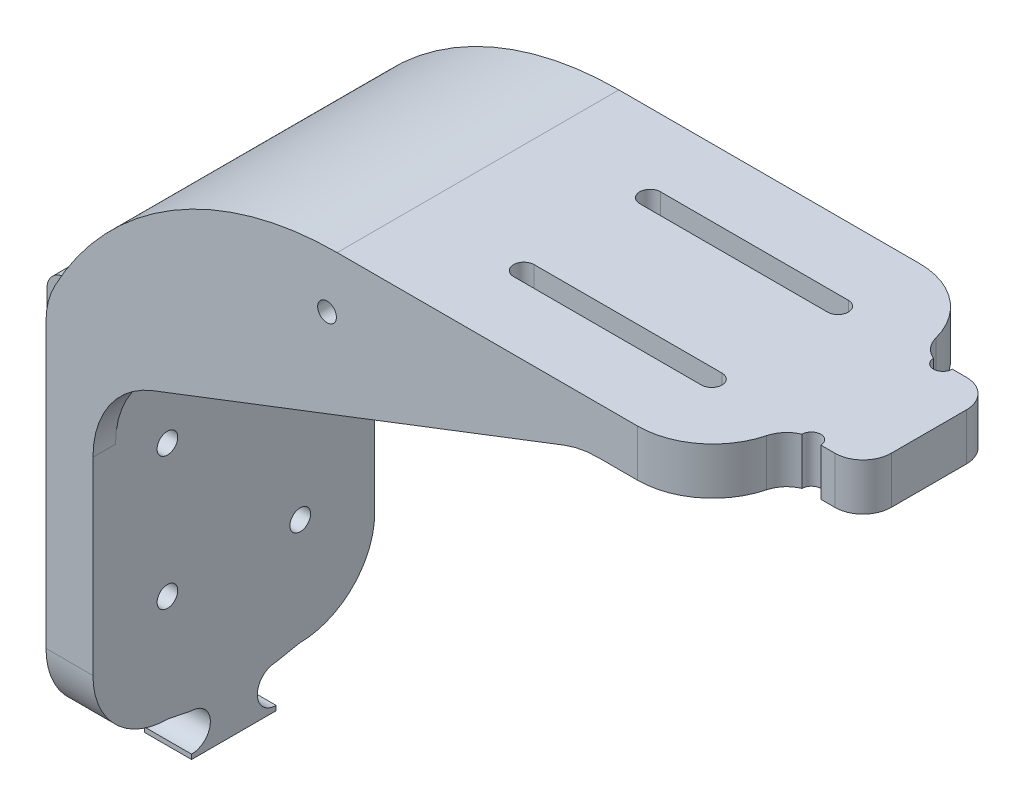
SolidWorks part; units mm, degrees
material "ABS"
ref_plane "Alzado" through (0, 0, 0) normal (0, 0, 1) x (1, 0, 0)
ref_plane "Planta" through (0, 0, 0) normal (0, 1, 0) x (1, 0, 0)
ref_plane "Vista lateral" through (0, 0, 0) normal (1, 0, 0) x (0, 0, -1)
sketch "Croquis1" plane through (0, 0, 0) normal (0, 0, 1) x (1, 0, 0)
  line L0 (0, 0) -> (0, 5)
  line L1 (0, 5) -> (-40, 5)
  line L2 (-40, 5) -> (-71, -15) construction
  line L3 (-71, -15) -> (-71, -55)
  line L4 (-71, -55) -> (-66, -55)
  line L5 (-66, -55) -> (-66, -16.0784)
  line L6 (-66, -16.0784) -> (-41.0784, 0) construction
  line L7 (-41.0784, 0) -> (0, 0)
  line L8 (-53.5392, -8.0392) -> (-39.986, -29.0466) construction
  arc A0 (-40, 5) -> (-71, -15) centre (-39.986, -29.0466) ccw
  arc A1 (-41.0784, 0) -> (-66, -16.0784) centre (-39.986, -29.0466) ccw
  dimension "D1" = 5
  dimension "D2" = 31
  dimension "D4" = 5
  dimension "D5" = 40
  dimension "D6" = 40
  dimension "D7" = 20
  dimension "D8" = 25
extrude "Saliente-Extruir1" add sketch "Croquis1" along normal blind 30
sketch "Croquis2" plane through (0, 5, 0) normal (0, 1, 0) x (1, 0, 0)
  line L0 (0, -30) -> (0, 0) construction
  line L1 (-18.4, -15) -> (-18.4, -12) construction
  line L2 (-18.4, -12) -> (-11.4, -12) construction
  line L4 (-11.4, -18) -> (-25.4, -18) construction
  line L6 (-25.4, -12) -> (-18.4, -12) construction
  line L7 (-18.4, -15) -> (-18.4, -8.28) construction
  line L8 (-18.4, -8.28) -> (-18.4, -7.18) construction
  line L9 (-18.4, -7.18) -> (-8.4, -7.18)
  line L11 (-8.4, -9.38) -> (-28.4, -9.38)
  line L13 (-28.4, -7.18) -> (-18.4, -7.18)
  line L14 (-18.4, -15) -> (-21.0577, -15) construction
  line L19 (-28.4, -9.38) -> (-28.4, -8.28) construction
  line L21 (-28.4, -8.28) -> (-28.4, -7.18) construction
  line L22 (0, -15) -> (-18.4, -15) construction
  line L23 (-8.4, -20.62) -> (-28.4, -20.62)
  line L24 (-18.4, -22.82) -> (-8.4, -22.82)
  line L25 (-28.4, -22.82) -> (-18.4, -22.82)
  circle A0 centre (-18.4, -15) radius 18.4 construction
  arc A1 (-25.4, -18) -> (-25.4, -12) centre (-25.4, -15) cw construction
  arc A2 (-11.4, -18) -> (-11.4, -12) centre (-11.4, -15) ccw construction
  arc A3 (-8.4, -9.38) -> (-8.4, -7.18) centre (-8.4, -8.28) ccw
  arc A4 (-28.4, -9.38) -> (-28.4, -7.18) centre (-28.4, -8.28) cw
  arc A9 (-8.4, -20.62) -> (-8.4, -22.82) centre (-8.4, -21.72) cw
  arc A10 (-28.4, -20.62) -> (-28.4, -22.82) centre (-28.4, -21.72) ccw
  point P28 (-18.4, -9.38)
  dimension "D1" = 36.8
  dimension "D5" = 3
  dimension "D6" = 3
  dimension "D2" = 18.4
  dimension "D3" = 3
  dimension "D4" = 6
  dimension "D7" = 7
  dimension "D8" = 7
  dimension "D9" = 6.72
  dimension "D10" = 2.2
  dimension "D13" = 10
  dimension "D14" = 10
  dimension "D15" = 20
extrude "Cortar-Extruir1" cut sketch "Croquis2" against normal up to vertex (5 mm away) up to point (0, 0, 30)
sketch "Croquis3" plane through (0, 0, 0) normal (0, -1, 0) x (1, 0, 0)
  line L0 (0, 30) -> (0, 0) construction
  line L5 (-28.4, 9.38) -> (-8.4, 9.38) construction
  line L6 (-33.5, 27.6) -> (-3.3, 27.6)
  line L7 (-33.5, 27.6) -> (-33.5, 2.4)
  line L8 (-33.5, 2.4) -> (-3.3, 2.4)
  line L9 (-3.3, 27.6) -> (-3.3, 2.4)
  line L10 (-33.5, 27.6) -> (-3.3, 2.4) construction
  line L11 (-33.5, 2.4) -> (-3.3, 27.6) construction
  line L12 (0, 15) -> (-18.4, 15) construction
  line L13 (-18.4, 15) -> (-18.4, 9.38) construction
  point P0 (-18.4, 15)
  dimension "D1" = 25.2
  dimension "D2" = 30.2
extrude "Cortar-Extruir2" cut sketch "Croquis3" against normal blind 2
sketch "Croquis4" plane through (-71, 0, 0) normal (-1, 0, 0) x (0, 0, 1)
  line L0 (30, -55) -> (0, -55) construction
  line L1 (15, -36.6) -> (21.5109, -36.6) construction
  line L3 (22.0711, -29.5289) -> (15, -36.6) construction
  circle A0 centre (15, -36.6) radius 18.4 construction
  circle A1 centre (22.0711, -29.5289) radius 1.1
  circle A2 centre (22.0711, -43.6711) radius 1.1
  circle A3 centre (7.9289, -43.6711) radius 1.1
  circle A4 centre (7.9289, -29.5289) radius 1.1
  circle A5 centre (15, -36.6) radius 3 construction
  point P15 (15, -36.6)
  dimension "D1" = 36.8
  dimension "D5" = 2.2
  dimension "D7" = 6
  dimension "D2" = 18.4
  dimension "D3" = 45
  dimension "D4" = 10
  dimension "D6" = 4
extrude "Cortar-Extruir3" cut sketch "Croquis4" against normal up to vertex (5 mm away) up to point (-66, -55, 30)
sketch "Croquis5" plane through (-71, 0, 0) normal (-1, 0, 0) x (0, 0, 1)
  line L1 (2.4, -49.2) -> (27.6, -49.2)
  line L2 (2.4, -49.2) -> (2.4, -24)
  line L3 (2.4, -24) -> (27.6, -24)
  line L4 (27.6, -49.2) -> (27.6, -24)
  line L5 (2.4, -49.2) -> (27.6, -24) construction
  line L6 (2.4, -24) -> (27.6, -49.2) construction
  circle A1 centre (22.0711, -29.5289) radius 1.1 construction
  circle A2 centre (7.9289, -29.5289) radius 1.1 construction
  point P0 (15, -36.6)
  dimension "D1" = 25.2
  dimension "D2" = 25.2
  dimension "D3" = 10
  dimension "D4" = 10
extrude "Cortar-Extruir4" cut sketch "Croquis5" against normal blind 2
fillet "Redondeo2" radius 8 5 edges at (-68.5, -55, 0) (-68.5, -55, 30) (0, 2.5, 0) (0, 2.5, 30) (-71, -15, 15)
fillet "Redondeo3" radius 2.7 8 edges at (-70, -49.2, 2.4) (-70, -24, 2.4) (-70, -24, 27.6) (-70, -49.2, 27.6) (-33.5, 1, 2.4) (-33.5, 1, 27.6) (-3.3, 1, 27.6) (-3.3, 1, 2.4)
sketch "Croquis6" plane through (0, 0, 0) normal (0, -1, 0) x (1, 0, 0)
  line L0 (0, 8) -> (0, 22)
  line L1 (0, 22) -> (8, 22)
  line L2 (8, 22) -> (8, 8)
  line L3 (8, 8) -> (0, 8)
  line L7 (0, 22) -> (0, 8) construction
  point P8 (0, 15)
  point P11 (0, 15)
  dimension "D2" = 14
  dimension "D1" = 8
extrude "Saliente-Extruir2" add sketch "Croquis6" against normal up to vertex (5 mm away) up to point (0, 5, 8)
fillet "Redondeo4" radius 3 2 edges at (8, 2.5, 22) (8, 2.5, 8)
sketch "Croquis11" plane through (0, 0, 30) normal (0, 0, 1) x (1, 0, 0)
  line L0 (-41.0784, 0) -> (-14.0784, 0)
  line L1 (-41.0784, 0) -> (-8, 0) construction
  line L2 (-14.0784, 0) -> (-66, -20)
  line L3 (-66, -47) -> (-66, -16.0784) construction
  line L4 (-66, -20) -> (-66, -16.0784)
  line L5 (0, 0) -> (0, -11) construction
  line L6 (0, -11) -> (-42.6353, -11) construction
  arc A2 (-41.0784, 0) -> (-66, -16.0784) centre (-39.986, -29.0466) ccw
  arc A3 (-41.0784, 0) -> (-66, -16.0784) centre (-39.986, -29.0466) ccw
  dimension "D1" = 35
  dimension "D2" = 27
  dimension "D4" = 11
  dimension "D3" = 0
extrude "Saliente-Extruir4" add sketch "Croquis11" against normal up to vertex (2.4 mm away) up to point (-6, 0, 27.6)
extrude "Saliente-Extruir5" add sketch "Croquis11<2>" along normal up to vertex (-27.6 mm away) from surface up to point (-6, 0, 2.4) starting at face at (-49.566, -13.598, 0)
sketch "Croquis11<2>" plane through (0, 0, 30) normal (0, 0, 1) x (1, 0, 0) same geometry as "Croquis11"
fillet "Redondeo5" radius 10 4 edges at (-14.0784, 0, 1.2) (-66, -20, 1.2) (-66, -20, 28.8) (-14.0784, 0, 28.8)
sketch "Croquis12" plane through (-71, 0, 0) normal (-1, 0, 0) x (0, 0, 1)
  line L0 (22, -55) -> (8, -55) construction
  line L1 (10.5, -55) -> (19.5, -55)
  line L3 (10.5, -60) -> (19.5, -60)
  line L8 (22, -55) -> (19.5, -55)
  line L10 (8, -55) -> (10.5, -55)
  line L11 (19.5, -55) -> (19.5, -60) construction
  line L12 (15, -60) -> (15, -55) construction
  line L13 (22, -55) -> (19.5, -55.5)
  line L14 (19.5, -59.5) -> (19.5, -60)
  line L15 (10.5, -59.5) -> (10.5, -60)
  line L16 (10.5, -55) -> (10.5, -60) construction
  line L17 (8, -55) -> (10.5, -55.5)
  arc A2 (19.5, -55.5) -> (19.5, -59.5) centre (19.5, -57.5) ccw
  arc A3 (10.5, -55.5) -> (10.5, -59.5) centre (10.5, -57.5) cw
  point P6 (15, -55)
  point P7 (15, -55)
  point P8 (15, -60)
  dimension "D3" = 2
  dimension "D1" = 9
  dimension "D2" = 5
extrude "Saliente-Extruir6" add sketch "Croquis12" against normal up to vertex (5 mm away) up to point (-66, -55, 8)
sketch "Croquis14" plane through (0, 0, 2.4) normal (0, 0, 1) x (1, 0, 0)
  line L0 (-41.0784, 0) -> (-41.0784, -2.01) construction
  circle A0 centre (-41.0784, -1.005) radius 1
  point P1 (0, 0)
  dimension "D1" = 2
extrude "Cortar-Extruir6" cut sketch "Croquis14" against normal up to vertex (2.4 mm away) and the other way up to vertex (27.6 mm away) up to point (-15.8136, -0.6684, 0) other way up to point (-15.8136, -0.6684, 30)
sketch "Croquis18" plane through (-71, 0, 0) normal (-1, 0, 0) x (0, 0, 1)
  line L0 (30, -16.8489) -> (0, -16.8489) construction
  line L1 (24.9, -24) -> (21.9, -24)
  line L2 (24.9, -24) -> (24.9, -16.8489)
  line L3 (24.9, -16.8489) -> (21.9, -16.8489)
  line L4 (21.9, -24) -> (21.9, -16.8489)
  dimension "D1" = 3
extrude "Saliente-Extruir7" add sketch "Croquis18" along normal blind 5
sketch "Croquis19" plane through (0, 0, 24.9) normal (0, 0, 1) x (1, 0, 0)
  line L0 (-71, -24) -> (-71, -16.8489) construction
  line L1 (-72.625, -22.0494) -> (-72.625, -24)
  line L2 (-76, -24) -> (-71, -24) construction
  line L3 (-72.625, -24) -> (-71, -24)
  line L4 (-71, -24) -> (-71, -20.4244)
  arc A0 (-71, -20.4244) -> (-72.625, -22.0494) centre (-72.625, -20.4244) ccw
  point P11 (-71, -20.4244)
  dimension "D1" = 3.25
extrude "Cortar-Extruir7" cut sketch "Croquis19" against normal up to vertex (3 mm away) up to point (-71, -24, 21.9)
sketch "Croquis20" plane through (0, 2, 0) normal (0, -1, 0) x (1, 0, 0)
  line L8 (-33.5, 24.9) -> (-33.5, 5.1)
  line L9 (-30.8, 2.4) -> (-6, 2.4)
  line L10 (-3.3, 5.1) -> (-3.3, 24.9)
  line L11 (-6, 27.6) -> (-30.8, 27.6)
  line L12 (-33.5, 24.9) -> (-33.5, 5.1)
  line L13 (-30.8, 2.4) -> (-6, 2.4)
  line L14 (-3.3, 5.1) -> (-3.3, 24.9)
  line L15 (-6, 27.6) -> (-30.8, 27.6)
  line L40 (-8.4, 22.82) -> (-28.4, 22.82)
  line L41 (-8.4, 22.82) -> (-28.4, 22.82)
  line L47 (-8.4, 20.62) -> (-28.4, 20.62) construction
  line L49 (-28.4, 7.18) -> (-8.4, 7.18)
  line L50 (-8.4, 9.38) -> (-28.4, 9.38)
  line L51 (-28.4, 7.18) -> (-8.4, 7.18)
  line L52 (-8.4, 9.38) -> (-28.4, 9.38)
  arc A8 (-33.5, 5.1) -> (-30.8, 2.4) centre (-30.8, 5.1) ccw
  arc A9 (-6, 2.4) -> (-3.3, 5.1) centre (-6, 5.1) ccw
  arc A10 (-3.3, 24.9) -> (-6, 27.6) centre (-6, 24.9) ccw
  arc A11 (-30.8, 27.6) -> (-33.5, 24.9) centre (-30.8, 24.9) ccw
  arc A12 (-33.5, 5.1) -> (-30.8, 2.4) centre (-30.8, 5.1) ccw
  arc A13 (-6, 2.4) -> (-3.3, 5.1) centre (-6, 5.1) ccw
  arc A14 (-3.3, 24.9) -> (-6, 27.6) centre (-6, 24.9) ccw
  arc A15 (-30.8, 27.6) -> (-33.5, 24.9) centre (-30.8, 24.9) ccw
  arc A38 (-8.4, 20.62) -> (-8.4, 22.82) centre (-8.4, 21.72) ccw
  arc A39 (-28.4, 22.82) -> (-28.4, 20.62) centre (-28.4, 21.72) ccw
  arc A40 (-8.4, 20.62) -> (-8.4, 22.82) centre (-8.4, 21.72) ccw
  arc A41 (-28.4, 22.82) -> (-28.4, 20.62) centre (-28.4, 21.72) ccw
  arc A46 (-8.4, 7.18) -> (-8.4, 9.38) centre (-8.4, 8.28) ccw
  arc A47 (-28.4, 9.38) -> (-28.4, 7.18) centre (-28.4, 8.28) ccw
  arc A48 (-8.4, 7.18) -> (-8.4, 9.38) centre (-8.4, 8.28) ccw
  arc A49 (-28.4, 9.38) -> (-28.4, 7.18) centre (-28.4, 8.28) ccw
  dimension "D4" = 25.2
  dimension "D5" = 30.2
  dimension "D6" = 20
  dimension "D7" = 11.24
  dimension "D1" = 0
  dimension "D2" = 0
  dimension "D3" = 0
sketch "Croquis22" plane through (0, 0, 0) normal (0, -1, 0) x (1, 0, 0)
  line L0 (5, 22) -> (0, 22) construction
  line L1 (8, 15) -> (0, 15) construction
  line L2 (8, 11) -> (8, 19) construction
  circle A0 centre (2.5, 22) radius 1
  circle A1 centre (2.5, 8) radius 1
  dimension "D1" = 2
extrude "Cortar-Extruir8" cut sketch "Croquis22" against normal up to surface (5 mm away) up to face at (-18.4, 5, 8.28)
fillet "Redondeo8" radius 2 2 edges at (-76, -16.8489, 23.4) (-76, -24, 23.4)
sketch "Croquis23" plane through (0, 0, 2.4) normal (0, 0, 1) x (1, 0, 0)
  line L0 (-41.0784, 0) -> (-30.8, 0)
  arc A0 (-41.0784, 0) -> (-50.8578, -2.0892) centre (-39.986, -29.0466) ccw
  arc A5 (-41.0784, 0) -> (-66, -16.0784) centre (-39.986, -29.0466) ccw construction
  point P5 (-62.1808, -10.2772)
  point P6 (0, 0)
  dimension "D1" = 10
sketch "Croquis24" plane through (-33.5, 0, 0) normal (1, 0, 0) x (0, 0, -1)
  line L0 (-15, 0) -> (-7, 0) construction
  line L1 (-24.9, 0) -> (-5.1, 0) construction
  line L2 (-15, 0) -> (-23, 0) construction
  line L3 (-15, 0) -> (-15, 1) construction
  line L4 (-7, 0) -> (-23, 0)
  arc A0 (-7, 0) -> (-23, 0) centre (-15, -31.5) ccw
  dimension "D1" = 8
  dimension "D2" = 1
sweep "Cortar-Barrer1" cut profiles "Croquis24" path "Croquis23"
fillet "Redondeo6" radius 3 2 edges at (0, 2.5, 8) (0, 2.5, 22)
